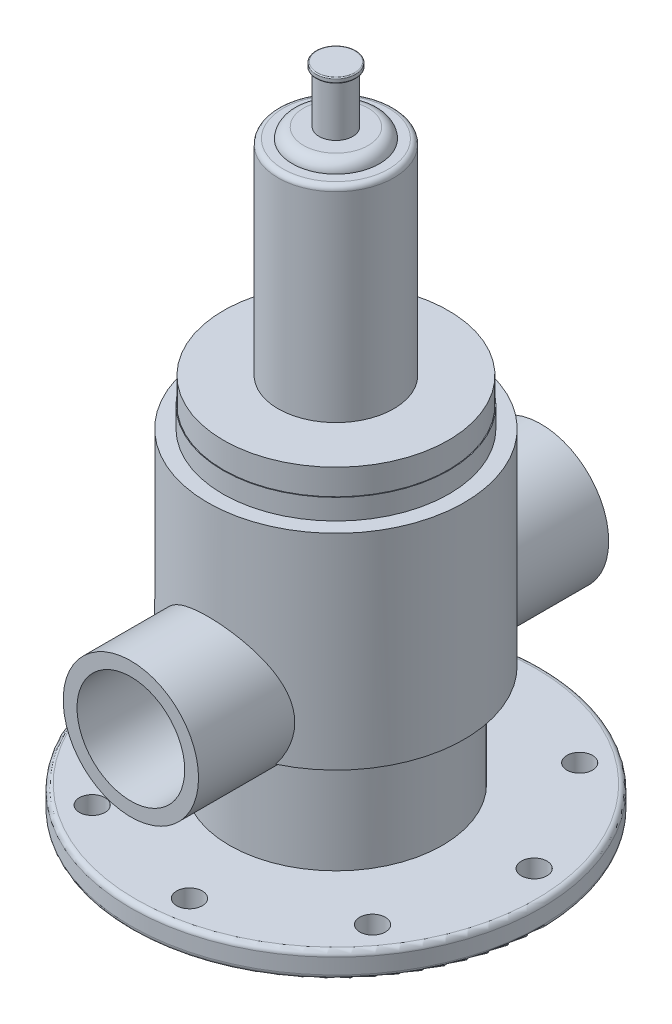
SolidWorks part; units mm, degrees
ref_plane "Front Plane" through (0, 0, 0) normal (0, 0, 1) x (1, 0, 0)
ref_plane "Top Plane" through (0, 0, 0) normal (0, 1, 0) x (1, 0, 0)
ref_plane "Right Plane" through (0, 0, 0) normal (1, 0, 0) x (0, 0, -1)
sketch "Sketch1" plane through (0, 0, 0) normal (0, 1, 0) x (1, 0, 0)
  circle A0 centre (0, 0) radius 50.8
  circle A1 centre (-6.413, 42.6928) radius 3.175
  circle A2 centre (25.6536, 34.723) radius 3.175
  circle A3 centre (42.6928, 6.413) radius 3.175
  circle A4 centre (34.723, -25.6536) radius 3.175
  circle A5 centre (6.413, -42.6928) radius 3.175
  circle A6 centre (-25.6536, -34.723) radius 3.175
  circle A7 centre (-42.6928, -6.413) radius 3.175
  circle A8 centre (-34.723, 25.6536) radius 3.175
  point P21 (0, 0)
  point P22 (0, 0)
  dimension "D1" = 8
  dimension "D2" = 6.35
extrude "Boss-Extrude1" add sketch "Sketch1" along normal blind 6.35
fillet "Fillet1" radius 1.27 1 edges at (0, 6.35, 50.8)
fillet "Fillet2" radius 1.27 1 edges at (0, 0, 50.8)
sketch "Sketch2" plane through (0, 6.35, 0) normal (0, 1, 0) x (1, 0, 0)
  circle A0 centre (0, 0) radius 26.3916
extrude "Boss-Extrude2" add sketch "Sketch2" along normal blind 25.4
sketch "Sketch3" plane through (0, 31.75, 0) normal (0, 1, 0) x (1, 0, 0)
  circle A0 centre (0, 0) radius 31.75
extrude "Boss-Extrude3" add sketch "Sketch3" along normal blind 50.8
sketch "Sketch4" plane through (0, 0, 0) normal (0, 0, 1) x (1, 0, 0)
  circle A0 centre (0, 41.3936) radius 13.335
  circle A1 centre (0, 41.3936) radius 16.764
extrude "Boss-Extrude4" add sketch "Sketch4" along normal blind 50.8 and the other way blind 50.8
sketch "Sketch5" plane through (0, 0, 0) normal (0, -1, 0) x (1, 0, 0)
  circle A0 centre (0, 0) radius 24.3159
extrude "Boss-Extrude5" add sketch "Sketch5" along normal blind 5.08
fillet "Fillet3" radius 2.54 1 edges at (0, -5.08, -24.3159)
sketch "Sketch6" plane through (0, 82.55, 0) normal (0, 1, 0) x (1, 0, 0)
  circle A0 centre (0, 0) radius 28.0275
extrude "Boss-Extrude6" add sketch "Sketch6" along normal blind 5.08
sketch "Sketch7" plane through (0, 87.63, 0) normal (0, 1, 0) x (1, 0, 0)
  circle A0 centre (0, 0) radius 27.8551
extrude "Boss-Extrude7" add sketch "Sketch7" along normal blind 6.35
sketch "Sketch8" plane through (0, 93.98, 0) normal (0, 1, 0) x (1, 0, 0)
  circle A0 centre (0, 0) radius 14.3299
extrude "Boss-Extrude8" add sketch "Sketch8" along normal blind 50.8
sketch "Sketch9" plane through (0, 144.78, 0) normal (0, 1, 0) x (1, 0, 0)
  circle A0 centre (0, 0) radius 10.7985
extrude "Boss-Extrude9" add sketch "Sketch9" along normal blind 2.54
sketch "Sketch10" plane through (0, 147.32, 0) normal (0, 1, 0) x (1, 0, 0)
  circle A0 centre (0, 0) radius 4.1673
extrude "Boss-Extrude10" add sketch "Sketch10" along normal blind 12.7
sketch "Sketch11" plane through (0, 160.02, 0) normal (0, 1, 0) x (1, 0, 0)
  circle A0 centre (0, 0) radius 4.9216
extrude "Boss-Extrude11" add sketch "Sketch11" along normal blind 1.27
fillet "Fillet7" radius 0.254 2 edges at (0, 160.02, 4.9216) (0, 161.29, 4.9216)
fillet "Fillet8" radius 2.794 1 edges at (0, 147.32, 10.7985)
fillet "Fillet9" radius 1.27 1 edges at (0, 144.78, 14.3299)
